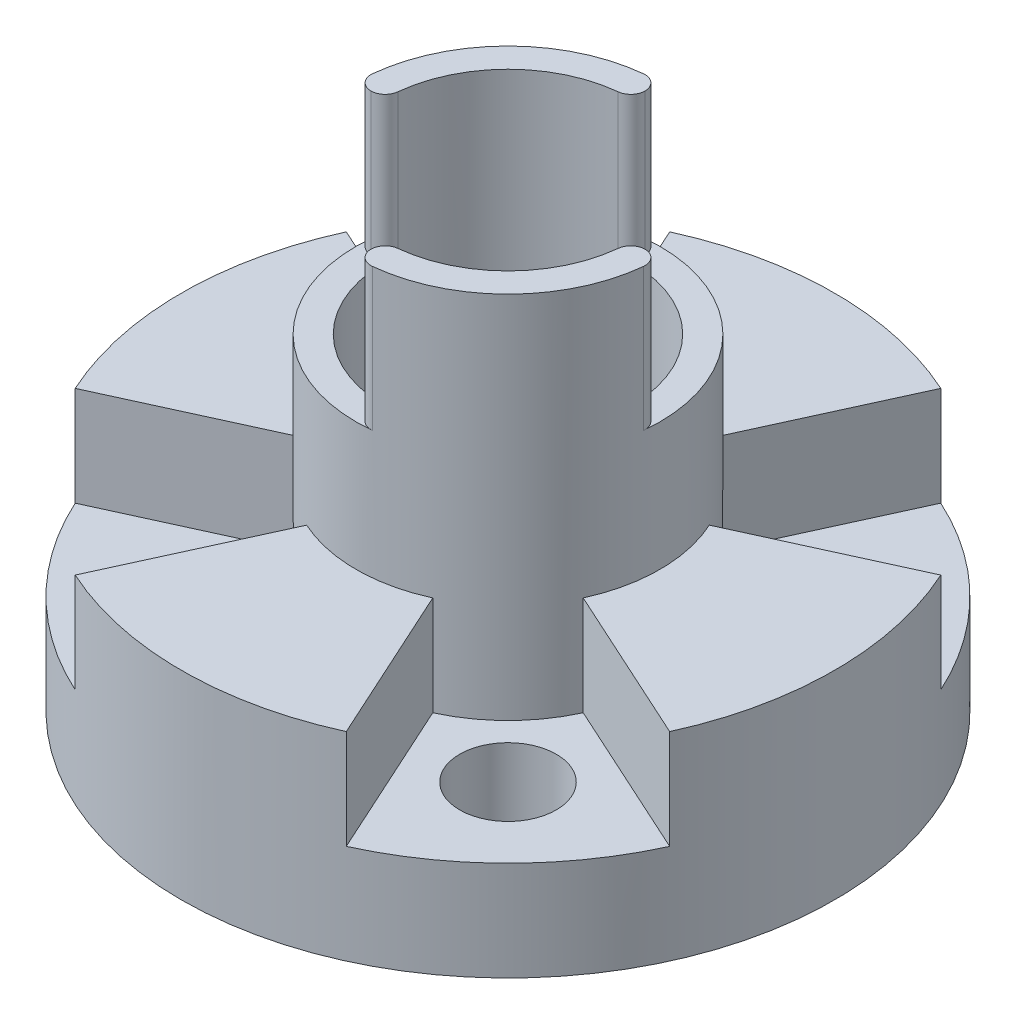
SolidWorks part; units mm, degrees
ref_plane "Alzado" through (0, 0, 0) normal (0, 0, 1) x (1, 0, 0)
ref_plane "Planta" through (0, 0, 0) normal (0, 1, 0) x (1, 0, 0)
ref_plane "Vista lateral" through (0, 0, 0) normal (1, 0, 0) x (0, 0, -1)
sketch "Croquis1" plane through (0, 0, 0) normal (0, 1, 0) x (1, 0, 0)
  line L0 (-8.3, -8.3) -> (8.3, 8.3) construction
  line L1 (-8.3, 8.3) -> (8.3, -8.3) construction
  circle A0 centre (0, 0) radius 4.35
  circle A1 centre (5.6569, 5.6569) radius 1.7
  circle A2 centre (-5.6569, 5.6569) radius 1.7
  circle A3 centre (-5.6569, -5.6569) radius 1.7
  circle A4 centre (5.6569, -5.6569) radius 1.7
  circle A5 centre (0, 0) radius 11.5
  dimension "D1" = 8.7
  dimension "D2" = 23
  dimension "D3" = 3.4
  dimension "D4" = 3.4
  dimension "D5" = 3.4
  dimension "D6" = 3.4
extrude "Saliente-Extruir1" add sketch "Croquis1" along normal blind 3.5
sketch "Croquis2" plane through (0, 3.5, 0) normal (0, 1, 0) x (1, 0, 0)
  circle A0 centre (0, 0) radius 4.35 construction
  circle A1 centre (0, 0) radius 4.35
  circle A2 centre (0, 0) radius 5.35
  dimension "D1" = 1
extrude "Saliente-Extruir2" add sketch "Croquis2" along normal blind 13
sketch "Croquis3" plane through (0, 16.5, 0) normal (0, 1, 0) x (1, 0, 0)
  line L0 (0, 5.35) -> (0, -5.35) construction
  line L1 (-5.35, 0) -> (5.35, 0) construction
  line L2 (0, 5.35) -> (0, 4.35)
  line L3 (5.35, 0) -> (4.35, 0)
  line L4 (0, -5.35) -> (0, -4.35)
  line L5 (-5.35, 0) -> (-4.35, 0)
  circle A0 centre (0, 0) radius 4.35 construction
  circle A1 centre (0, 0) radius 5.35 construction
  arc A2 (-4.35, 0) -> (0, -4.35) centre (0, 0) ccw
  arc A3 (-5.35, 0) -> (0, -5.35) centre (0, 0) ccw
  arc A4 (4.35, 0) -> (0, 4.35) centre (0, 0) ccw
  arc A5 (5.35, 0) -> (0, 5.35) centre (0, 0) ccw
extrude "Cortar-Extruir1" cut sketch "Croquis3" against normal blind 5
sketch "Croquis4" plane through (0, 0, 0) normal (0, -1, 0) x (1, 0, 0)
  circle A0 centre (0, 0) radius 4.35 construction
  circle A1 centre (0, 0) radius 4.35
  circle A2 centre (0, 0) radius 5.275
  dimension "D1" = 10.55
extrude "Cortar-Extruir2" cut sketch "Croquis4" against normal blind 2
fillet "Redondeo1" radius 0.6 1 edges at (0, 0, -5.275)
fillet "Redondeo2" radius 0.5 8 edges at (-4.35, 14, 0) (-5.35, 14, 0) (0, 14, 5.35) (0, 14, 4.35) (0, 14, -4.35) (0, 14, -5.35) (4.35, 14, 0) (5.35, 14, 0)
sketch "Croquis5" plane through (0, 3.5, 0) normal (0, 1, 0) x (1, 0, 0)
  line L0 (0, 11.5) -> (0, -11.5) construction
  line L1 (11.5, 0) -> (-11.5, 0) construction
  line L2 (0, 0) -> (-10.4635, 4.7713) construction
  line L3 (0, 0) -> (-10.4635, -4.7713) construction
  line L4 (0, 0) -> (10.4635, -4.7713) construction
  line L5 (0, 0) -> (10.4635, 4.7713) construction
  line L6 (0, 0) -> (-4.7713, 10.4635) construction
  line L7 (0, 0) -> (4.7713, 10.4635) construction
  line L8 (0, 0) -> (-4.7713, -10.4635) construction
  line L9 (0, 0) -> (4.7713, -10.4635) construction
  line L10 (-4.7713, 10.4635) -> (-2.2197, 4.8678)
  line L11 (4.7713, 10.4635) -> (2.2197, 4.8678)
  line L12 (10.4635, 4.7713) -> (4.8678, 2.2197)
  line L13 (10.4635, -4.7713) -> (4.8678, -2.2197)
  line L14 (4.7713, -10.4635) -> (2.2197, -4.8678)
  line L15 (-4.7713, -10.4635) -> (-2.2197, -4.8678)
  line L16 (-10.4635, -4.7713) -> (-4.8678, -2.2197)
  line L17 (-10.4635, 4.7713) -> (-4.8678, 2.2197)
  circle A0 centre (0, 0) radius 11.5 construction
  circle A1 centre (0, 0) radius 5.35 construction
  circle A2 centre (0, 0) radius 11.5
  arc A3 (2.2197, 4.8678) -> (-2.2197, 4.8678) centre (0, 0) ccw
  circle A5 centre (-5.6569, 5.6569) radius 1.7 construction
  circle A6 centre (-5.6569, -5.6569) radius 1.7 construction
  circle A7 centre (5.6569, -5.6569) radius 1.7 construction
  circle A8 centre (5.6569, 5.6569) radius 1.7 construction
  arc A9 (4.8678, -2.2197) -> (4.8678, 2.2197) centre (0, 0) ccw
  arc A10 (-2.2197, -4.8678) -> (2.2197, -4.8678) centre (0, 0) ccw
  arc A11 (-4.8678, 2.2197) -> (-4.8678, -2.2197) centre (0, 0) ccw
  circle M11 centre (0, 0) radius 11.5
  circle M14 centre (0, 0) radius 5.35
  dimension "D1" = 2.8
  dimension "D2" = 2.8
  dimension "D7" = 2.8
  dimension "D8" = 2.8
  dimension "D3" = 2.8
  dimension "D4" = 2.8
  dimension "D5" = 2.8
  dimension "D6" = 2.8
extrude "Saliente-Extruir3" add sketch "Croquis5" along normal blind 3.5 contours L17 L16 M11 M14 | L15 L14 M11 M14 | L13 L12 M11 M14 | L11 L10 M11 M14 region at (0, 3.5, -8.5331) region at (-8.5331, 3.5, 0) region at (8.5331, 3.5, 0) region at (0, 3.5, 8.5331)
